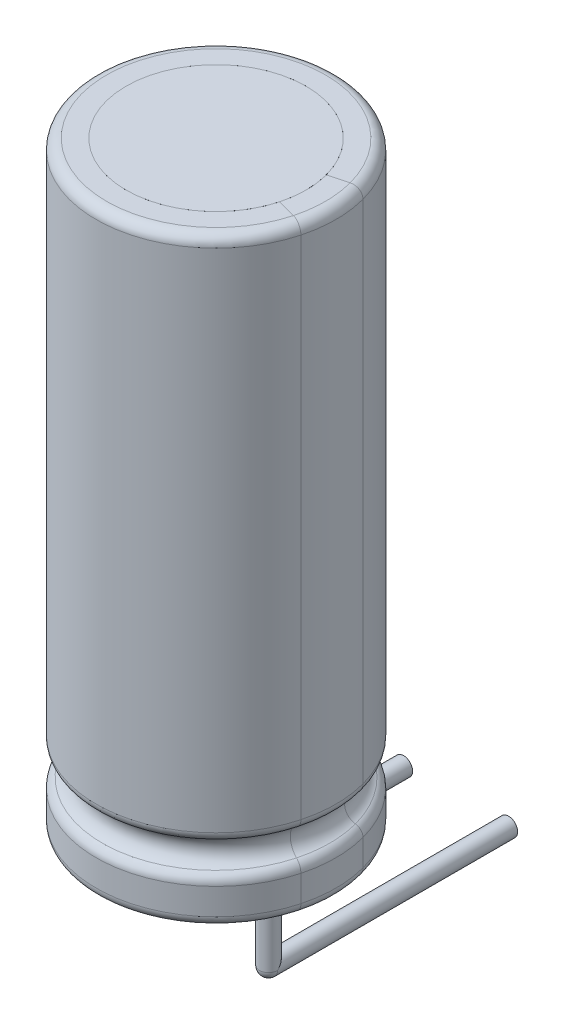
SolidWorks part; units mm, degrees
ref_plane "Alzado" through (0, 0, 0) normal (0, 0, 1) x (1, 0, 0)
ref_plane "Planta" through (0, 0, 0) normal (0, 1, 0) x (1, 0, 0)
ref_plane "Vista lateral" through (0, 0, 0) normal (1, 0, 0) x (0, 0, -1)
sketch "Croquis1" plane through (0, 0, 0) normal (0, 1, 0) x (1, 0, 0)
  line L1 (2.8978, 0.7765) -> (3.8637, 1.0353)
  line L2 (2.8978, -0.7765) -> (3.8637, -1.0353)
  circle A0 centre (0, 0) radius 4
  circle A1 centre (0, 0) radius 3
  dimension "D1" = 8
  dimension "D2" = 6
extrude "Saliente-Extruir3" add sketch "Croquis1" along normal blind 20 contours A1 L2 A0 L1 region at (3.4837, 0, 0)
extrude "Saliente-Extruir4" add sketch "Croquis1<5>" along normal blind 20 separate body contours A1 region at (0, 0, 0)
sketch "Croquis1<5>" plane through (0, 0, 0) normal (0, 1, 0) x (1, 0, 0) same geometry as "Croquis1"
extrude "Saliente-Extruir5" add sketch "Croquis1<6>" along normal blind 20 separate body contours A1 L1 A0 L2 region at (-3.1122, 0, 0)
sketch "Croquis1<6>" plane through (0, 0, 0) normal (0, 1, 0) x (1, 0, 0) same geometry as "Croquis1"
sketch "Croquis3" plane through (0, 0, 0) normal (1, 0, 0) x (0, 0, -1)
  line L0 (0, -1.736) -> (0, 22.3491)
  line L1 (-4, 20) -> (-4, 0) construction
  line L2 (-4, 0) -> (4, 0) construction
  circle A0 centre (-4, 2) radius 0.5
  dimension "D1" = 2
revolve "Cortar-Revolución1" cut sketch "Croquis3" angle 360 about L0
fillet "Redondeo1" radius 0.35 4 edges at (-4, 0, 0) (-4, 1.5, 0) (-4, 2.5, 0) (-4, 20, 0)
fillet "Redondeo2" radius 0.35 4 edges at (4, 0, 0) (4, 1.5, 0) (4, 2.5, 0) (4, 20, 0)
sketch "Croquis4" plane through (0, 0, 0) normal (0, -1, 0) x (1, 0, 0)
  circle A1 centre (-1.75, 0) radius 0.3011
  circle A2 centre (1.75, 0) radius 0.303
extrude "Saliente-Extruir6" add sketch "Croquis4" along normal blind 3 separate body contours A2 | A1
sketch "Croquis5" plane through (0, 0, 0) normal (0, 0, 1) x (1, 0, 0)
  line L0 (-2.0511, -3) -> (-1.4489, -3) construction
  line L1 (1.447, -3) -> (2.053, -3) construction
  circle A0 centre (-1.75, -3) radius 0.3011
  circle A1 centre (1.75, -3) radius 0.303
extrude "Saliente-Extruir7" add sketch "Croquis5" against normal blind 8 contours A1 | A0
sketch "Croquis6" plane through (0, 0, 0) normal (0, 0, 1) x (1, 0, 0)
  line L0 (-1.4489, -3) -> (-2.0511, -3) construction
  line L1 (2.053, -3) -> (1.447, -3) construction
  line L2 (-1.4489, -3) -> (-2.0511, -3)
  line L3 (2.053, -3) -> (1.447, -3)
  arc A0 (-2.0511, -3) -> (-1.4489, -3) centre (-1.75, -3) ccw construction
  arc A1 (1.447, -3) -> (2.053, -3) centre (1.75, -3) ccw construction
  arc A2 (-2.0511, -3) -> (-1.4489, -3) centre (-1.75, -3) ccw
  arc A3 (1.447, -3) -> (2.053, -3) centre (1.75, -3) ccw
revolve "Revolución1" add sketch "Croquis6" angle 360 about L3
